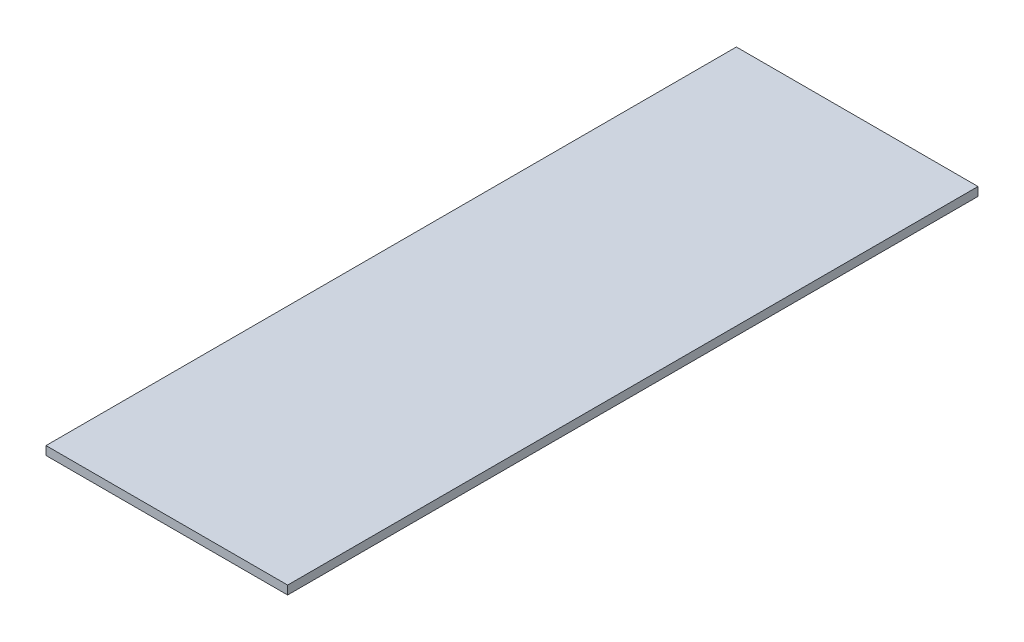
SolidWorks part; units mm, degrees
ref_plane "Front Plane" through (0, 0, 0) normal (0, 0, 1) x (1, 0, 0)
ref_plane "Top Plane" through (0, 0, 0) normal (0, 1, 0) x (1, 0, 0)
ref_plane "Right Plane" through (0, 0, 0) normal (1, 0, 0) x (0, 0, -1)
sketch "Sketch1" plane through (0, 0, 0) normal (0, 1, 0) x (1, 0, 0)
  line L1 (-70, -200) -> (70, -200)
  line L2 (-70, -200) -> (-70, 200)
  line L3 (-70, 200) -> (70, 200)
  line L4 (70, -200) -> (70, 200)
  line L5 (-70, -200) -> (70, 200) construction
  line L6 (-70, 200) -> (70, -200) construction
  point P0 (0, 0)
  dimension "D1" = 140
  dimension "D2" = 400
extrude "Boss-Extrude1" add sketch "Sketch1" along normal blind 5
